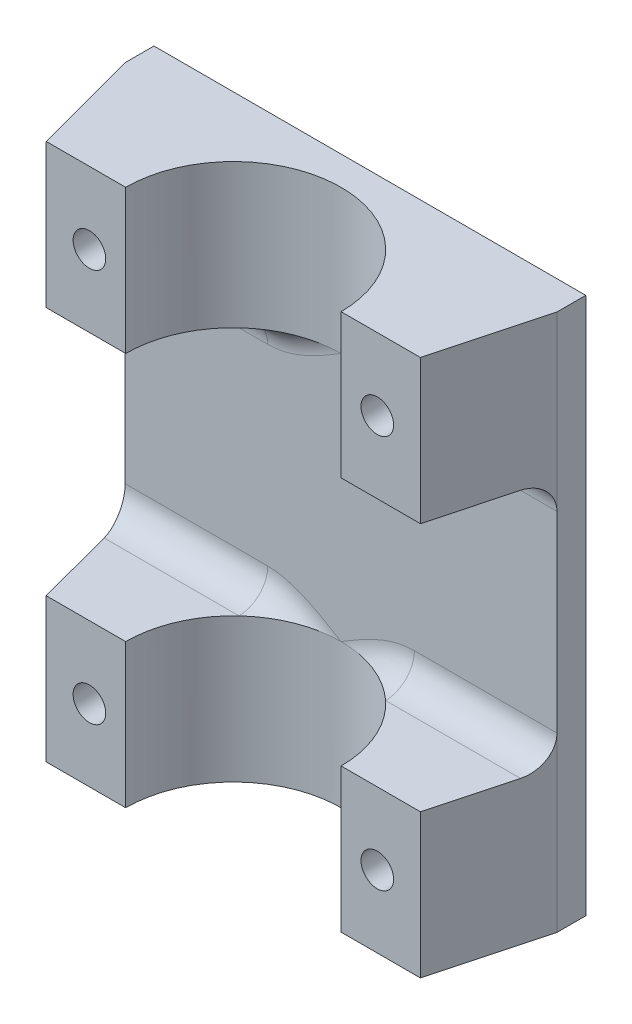
SolidWorks part; units mm, degrees
ref_plane "Ön Düzlem" through (0, 0, 0) normal (0, 0, 1) x (1, 0, 0)
ref_plane "Üst Düzlem" through (0, 0, 0) normal (0, 1, 0) x (1, 0, 0)
ref_plane "Sağ Düzlem" through (0, 0, 0) normal (1, 0, 0) x (0, 0, -1)
sketch "Çizim1" plane through (0, 0, 0) normal (0, 0, 1) x (1, 0, 0)
  line L0 (0, 56) -> (0, 0)
  line L5 (7.5, 48.5) -> (37.5, 48.5) construction
  line L6 (7.5, 48.5) -> (7.5, 7.5) construction
  line L7 (7.5, 7.5) -> (37.5, 7.5) construction
  line L8 (37.5, 48.5) -> (37.5, 7.5) construction
  line L9 (0, 0) -> (45, 0)
  line L10 (45, 56) -> (45, 0)
  line L11 (0, 56) -> (45, 56)
  circle A0 centre (7.5, 48.5) radius 1.7
  circle A1 centre (7.5, 7.5) radius 1.7
  circle A2 centre (37.5, 48.5) radius 1.7
  circle A3 centre (37.5, 7.5) radius 1.7
  dimension "D1" = 41
  dimension "D4" = 3.4
  dimension "D2" = 30
  dimension "D3" = 7.5
extrude "Yükseklik-Ekstrüzyon1" add sketch "Çizim1" along normal blind 3
sketch "Çizim2" plane through (0, 56, 0) normal (0, 1, 0) x (1, 0, 0)
  line L1 (22.5, -3) -> (22.5, -14.225) construction
  line L2 (45, -3) -> (0, -3) construction
  line L3 (11.275, -14.225) -> (33.725, -14.225)
  line L4 (0, -3) -> (3, -14.225)
  line L5 (0, -3) -> (45, -3)
  line L6 (3, -14.225) -> (11.275, -14.225)
  line L7 (33.725, -14.225) -> (42, -14.225)
  line L8 (42, -14.225) -> (45, -3)
  line L9 (0, -3) -> (0, 0) construction
  arc A1 (33.725, -14.225) -> (11.275, -14.225) centre (22.5, -14.225) ccw
  line M10 (0, -3) -> (45, -3)
  dimension "D1" = 22.45
  dimension "D2" = 3
  dimension "D3" = 3
extrude "Yükseklik-Ekstrüzyon2" add sketch "Çizim2" against normal up to surface (56 mm away) contours A1 L7 L8 L5 | A1 L4 L6 M10 up to face at (22.5, 0, 1.5)
sketch "Çizim4" plane through (0, 0, 3) normal (0, 0, -1) x (-1, 0, 0)
  circle A0 centre (-37.5, 7.5) radius 1.7 construction
  circle A1 centre (-7.5, 7.5) radius 1.7 construction
  circle A2 centre (-7.5, 48.5) radius 1.7 construction
  circle A3 centre (-37.5, 48.5) radius 1.7 construction
  circle A4 centre (-37.5, 7.5) radius 1.7
  circle A5 centre (-7.5, 7.5) radius 1.7
  circle A6 centre (-7.5, 48.5) radius 1.7
  circle A7 centre (-37.5, 48.5) radius 1.7
extrude "Kes-Ekstrüzyon2" cut sketch "Çizim4" against normal blind 55
sketch "Çizim5" plane through (0, 0, 0) normal (-1, 0, 0) x (0, 0, 1)
  line L0 (3, 56) -> (3, 0) construction
  line L1 (3, 41) -> (14.225, 41)
  line L2 (3, 41) -> (3, 15)
  line L3 (3, 15) -> (14.225, 15)
  line L4 (14.225, 41) -> (14.225, 15)
  line L5 (14.225, 0) -> (14.225, 56) construction
  line L6 (3, 56) -> (14.225, 56) construction
  line L7 (14.225, 0) -> (3, 0) construction
  dimension "D1" = 15
  dimension "D2" = 15
extrude "Kes-Ekstrüzyon3" cut sketch "Çizim5" against normal blind 55
fillet "Radyus1" radius 3 4 edges at (33.75, 15, 3) (33.75, 41, 3) (11.25, 15, 3) (11.25, 41, 3)
